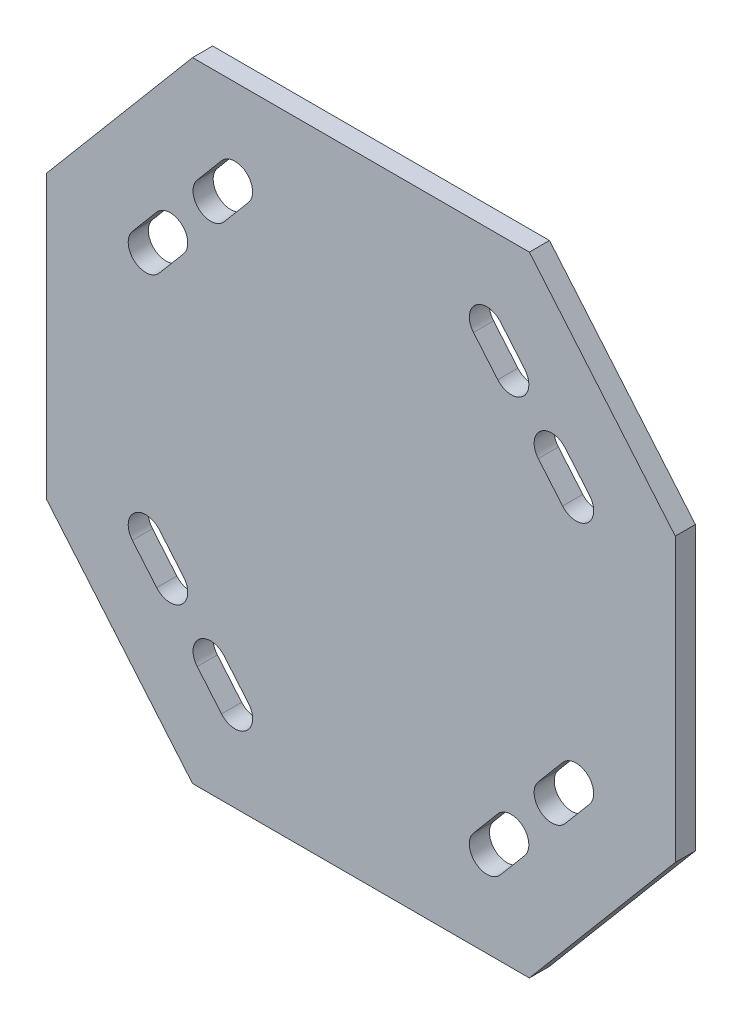
SolidWorks part; units mm, degrees
material "Простая углеродистая сталь"
ref_plane "Спереди" through (0, 0, 0) normal (0, 0, 1) x (1, 0, 0)
ref_plane "Сверху" through (0, 0, 0) normal (0, 1, 0) x (1, 0, 0)
ref_plane "Справа" through (0, 0, 0) normal (1, 0, 0) x (0, 0, -1)
sketch "Эскиз1" plane through (0, 0, 0) normal (0, 0, 1) x (1, 0, 0)
  line L1 (0, 0) -> (250, 0)
  line L2 (0, 0) -> (0, -250)
  line L3 (0, -250) -> (250, -250)
  line L4 (250, 0) -> (250, -250)
  dimension "D1" = 250
  dimension "D2" = 250
base flange "Базовая кромка1" sketch "Эскиз1" thickness 8 reverse thickness direction no parameters "D1"=1
sketch "Эскиз2" plane through (0, 0, 0) normal (0, 0, 1) x (1, 0, 0)
  line L0 (58.0221, 0) -> (0, -68.8)
  line L1 (250, 0) -> (0, 0) construction
  line L2 (0, -68.8) -> (0, 0)
  line L3 (0, 0) -> (58.0221, 0)
  line L4 (125, 0) -> (125, -75.5488) construction
  line L5 (250, 0) -> (191.9779, 0)
  line L6 (250, -68.8) -> (250, 0)
  line L7 (191.9779, 0) -> (250, -68.8)
  line L8 (0, -125) -> (66.8204, -125) construction
  line L9 (0, 0) -> (0, -250) construction
  line L10 (191.9779, -250) -> (250, -181.2)
  line L11 (250, -181.2) -> (250, -250)
  line L12 (250, -250) -> (191.9779, -250)
  line L13 (0, -250) -> (58.0221, -250)
  line L14 (0, -181.2) -> (0, -250)
  line L15 (58.0221, -250) -> (0, -181.2)
  dimension "D1" = 90
  dimension "D2" = 68.8
extrude "Вырез-Вытянуть1" cut sketch "Эскиз2" against normal blind 10 normal cut yes
sketch "Эскиз3" plane through (0, 0, -8) normal (0, 0, -1) x (-1, 0, 0)
  line L0 (-74.9084, -34.2667) -> (-65.238, -45.7333) construction
  line L1 (-69.5573, -29.7538) -> (-59.8869, -41.2205)
  line L2 (-80.2595, -38.7795) -> (-70.5891, -50.2462)
  line L3 (0, -68.8) -> (-58.0221, 0) construction
  line L4 (-49.1208, -64.8444) -> (-39.4504, -76.3111) construction
  line L5 (-43.7697, -60.3316) -> (-34.0993, -71.7983)
  line L6 (-54.4719, -69.3573) -> (-44.8015, -80.8239)
  line L7 (-125, 0) -> (-125, -250) construction
  line L8 (-191.9779, 0) -> (-58.0221, 0) construction
  line L9 (-58.0221, -250) -> (-191.9779, -250) construction
  line L10 (0, -125) -> (-77.0868, -125) construction
  line L11 (0, -68.8) -> (0, -181.2) construction
  line L12 (-175.0916, -34.2667) -> (-184.762, -45.7333) construction
  line L13 (-180.4427, -29.7538) -> (-190.1131, -41.2205)
  line L14 (-169.7405, -38.7795) -> (-179.4109, -50.2462)
  line L15 (-200.8792, -64.8444) -> (-210.5496, -76.3111) construction
  line L16 (-206.2303, -60.3316) -> (-215.9007, -71.7983)
  line L17 (-195.5281, -69.3573) -> (-205.1985, -80.8239)
  line L18 (-74.9084, -215.7333) -> (-65.238, -204.2667) construction
  line L19 (-69.5573, -220.2462) -> (-59.8869, -208.7795)
  line L20 (-80.2595, -211.2205) -> (-70.5891, -199.7538)
  line L21 (-49.1208, -185.1556) -> (-39.4504, -173.6889) construction
  line L22 (-43.7697, -189.6684) -> (-34.0993, -178.2017)
  line L23 (-54.4719, -180.6427) -> (-44.8015, -169.1761)
  line L24 (-175.0916, -215.7333) -> (-184.762, -204.2667) construction
  line L25 (-180.4427, -220.2462) -> (-190.1131, -208.7795)
  line L26 (-169.7405, -211.2205) -> (-179.4109, -199.7538)
  line L27 (-200.8792, -185.1556) -> (-210.5496, -173.6889) construction
  line L28 (-206.2303, -189.6684) -> (-215.9007, -178.2017)
  line L29 (-195.5281, -180.6427) -> (-205.1985, -169.1761)
  arc A0 (-69.5573, -29.7538) -> (-80.2595, -38.7795) centre (-74.9084, -34.2667) ccw
  arc A1 (-70.5891, -50.2462) -> (-59.8869, -41.2205) centre (-65.238, -45.7333) ccw
  arc A2 (-43.7697, -60.3316) -> (-54.4719, -69.3573) centre (-49.1208, -64.8444) ccw
  arc A3 (-44.8015, -80.8239) -> (-34.0993, -71.7983) centre (-39.4504, -76.3111) ccw
  arc A4 (-180.4427, -29.7538) -> (-169.7405, -38.7795) centre (-175.0916, -34.2667) cw
  arc A5 (-179.4109, -50.2462) -> (-190.1131, -41.2205) centre (-184.762, -45.7333) cw
  arc A6 (-206.2303, -60.3316) -> (-195.5281, -69.3573) centre (-200.8792, -64.8444) cw
  arc A7 (-205.1985, -80.8239) -> (-215.9007, -71.7983) centre (-210.5496, -76.3111) cw
  arc A8 (-69.5573, -220.2462) -> (-80.2595, -211.2205) centre (-74.9084, -215.7333) cw
  arc A9 (-70.5891, -199.7538) -> (-59.8869, -208.7795) centre (-65.238, -204.2667) cw
  arc A10 (-43.7697, -189.6684) -> (-54.4719, -180.6427) centre (-49.1208, -185.1556) cw
  arc A11 (-44.8015, -169.1761) -> (-34.0993, -178.2017) centre (-39.4504, -173.6889) cw
  arc A12 (-180.4427, -220.2462) -> (-169.7405, -211.2205) centre (-175.0916, -215.7333) ccw
  arc A13 (-179.4109, -199.7538) -> (-190.1131, -208.7795) centre (-184.762, -204.2667) ccw
  arc A14 (-206.2303, -189.6684) -> (-195.5281, -180.6427) centre (-200.8792, -185.1556) ccw
  arc A15 (-205.1985, -169.1761) -> (-215.9007, -178.2017) centre (-210.5496, -173.6889) ccw
  point P2 (-70.0732, -40)
  point P12 (-44.2856, -70.5778)
  point P29 (-179.9268, -40)
  point P36 (-205.7144, -70.5778)
  point P43 (-70.0732, -210)
  point P50 (-44.2856, -179.4222)
  point P57 (-179.9268, -210)
  point P64 (-205.7144, -179.4222)
  dimension "D1" = 7
  dimension "D4" = 15
  dimension "D2" = 35
  dimension "D3" = 40
  dimension "D5" = 40
extrude "Вырез-Вытянуть2" cut sketch "Эскиз3" against normal blind 10 normal cut yes
sketch "Сгиб-Линии1" [suppressed] plane through (0, 0, 0) normal (0, 1, 0) x (1, 0, 0)
sketch "Граничная рамка1" [suppressed] plane through (0, 0, 0) normal (0, 1, 0) x (1, 0, 0)
sheet metal parameters "Листовой металл1" thickness 8 parameters "D1"=1
flat pattern "Развертка1" [suppressed]
sketch "Сгиб-Линии2" plane through (0, 0, 0) normal (0, 1, 0) x (1, 0, 0)
sketch "Граничная рамка2" [suppressed] plane through (0, 0, 0) normal (0, 1, 0) x (1, 0, 0)
sheet metal parameters "Листовой металл2" thickness 8 parameters "D1"=1
flat pattern "Развертка1"
sketch "Сгиб-Линии2" plane through (0, 0, 0) normal (0, 1, 0) x (1, 0, 0)
sketch "Граничная рамка2" [suppressed] plane through (0, 0, 0) normal (0, 1, 0) x (1, 0, 0)
sheet metal parameters "Листовой металл3" thickness 8 parameters "D1"=1
flat pattern "Развертка1"
sketch "Сгиб-Линии2" plane through (0, 0, 0) normal (0, 1, 0) x (1, 0, 0)
sketch3d "Граничная рамка2" [suppressed]
  line L0 (0, -250, 0) -> (250, -250, 0) construction
  line L1 (0, 0, 0) -> (250, 0, 0) construction
  line L2 (0, -250, 0) -> (0, 0, 0) construction
  line L3 (250, -250, 0) -> (250, 0, 0) construction
